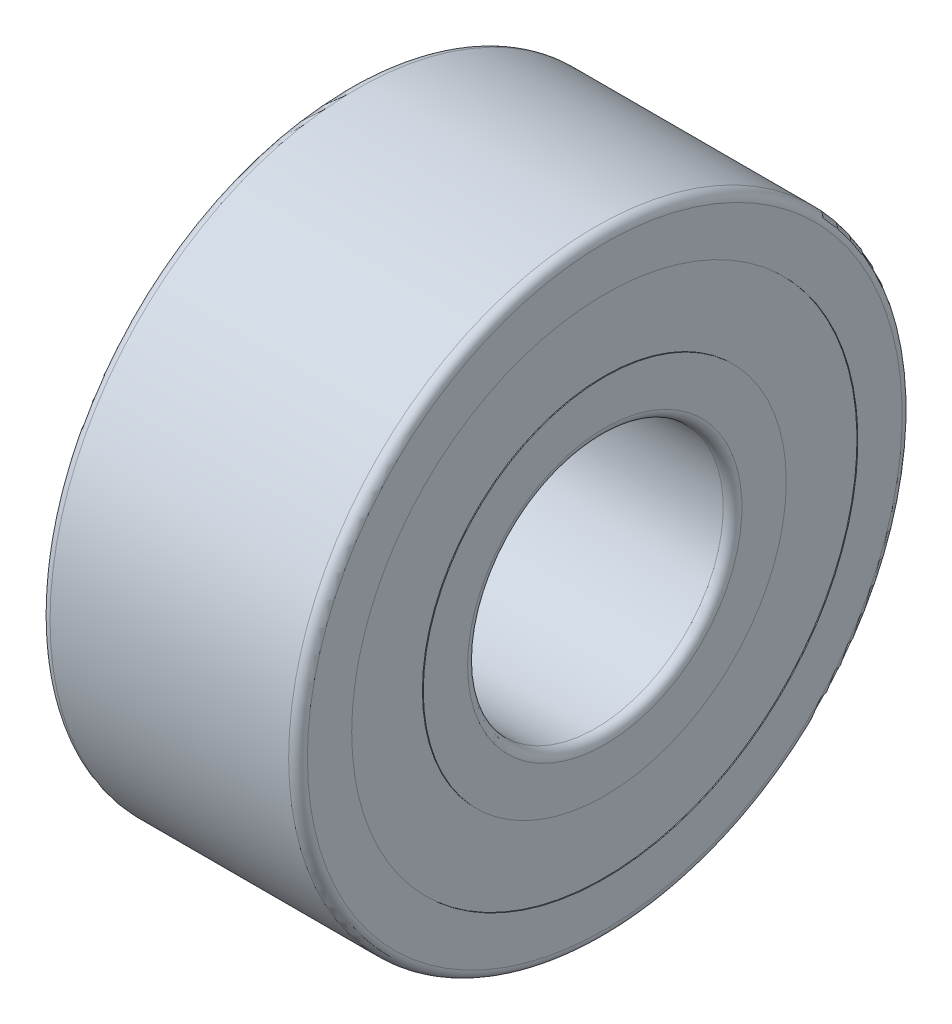
SolidWorks part; units mm, degrees
note: '?' marks a value the reader was unsure of.
ref_plane "基准面1" through (0, 0, 0) normal (0, 0, 1) x (1, 0, 0)
ref_plane "基准面2" through (0, 0, 0) normal (0, 1, 0) x (1, 0, 0)
ref_plane "基准面3" through (0, 0, 0) normal (1, 0, 0) x (0, 0, -1)
sketch "尺寸草图" plane through (0, 0, 0) normal (0, 0, 1) x (1, 0, 0)
  line L0 (0, 0) -> (72, 0) construction
  point P3 (1.1, 0)
  point P4 (30.2, 0)
  point P5 (30, 0)
  dimension "DD" = 72
  dimension "r" = 1.1
  dimension "B" = 30.2
  dimension "d" = 30
sketch "草图1" plane through (0, 0, 0) normal (0, 0, 1) x (1, 0, 0)
  line L0 (0, 0) -> (30.2, 0) construction
  line L1 (0, 0) -> (0, 36) construction
  line L2 (0, 25.5) -> (30.2, 25.5) construction
  line L3 (0, 15) -> (30.2, 15)
  line L4 (0, 36) -> (30.2, 36)
  line L5 (0, 36) -> (0, 15)
  line L6 (30.2, 36) -> (30.2, 15)
  line L7 (7.55, 36) -> (7.55, 15) construction
  line L8 (29.45, 29.7) -> (29.45, 21.3)
  line L9 (15.1, 36) -> (15.1, 15) construction
  line L10 (7.55, 21.3) -> (30.2, 21.3)
  line L11 (7.55, 29.7) -> (30.2, 29.7)
  circle A1 centre (7.55, 25.5) radius 6.3
  circle A3 centre (22.65, 25.5) radius 6.3
  dimension "D4" = 30
  dimension "D2" = 12.6
  dimension "D3" = 30.2
  dimension "D1" = 72
  dimension "D7" = 7.55
  dimension "D9" = 0.75
  dimension "D5" = 4.2
  dimension "D6" = 4.2
sketch "草图2" plane through (0, 0, 0) normal (0, 0, 1) x (1, 0, 0)
  line L2 (0, 36) -> (30.2, 36) construction
  line L3 (7.55, 29.7) -> (30.2, 29.7) construction
  line L4 (30.2, 36) -> (30.2, 15) construction
  line L6 (0, 36) -> (30.2, 36)
  line L7 (0, 29.7) -> (30.2, 29.7)
  line L8 (30.2, 36) -> (30.2, 29.7)
  line L9 (0, 36) -> (0, 29.7)
  line L10 (0, 0) -> (72, 0) construction
  line L11 (0, 0) -> (72, 0) construction
revolve "基体-旋转" add sketch "草图2" angle 360 about L11
sketch "草图4" plane through (0, 0, 0) normal (0, 0, 1) x (1, 0, 0)
  line L0 (0, 36) -> (0, -36) construction
  line L1 (30.2, 36) -> (30.2, 15) construction
  line L2 (7.55, 21.3) -> (30.2, 21.3) construction
  line L3 (0, 0) -> (30.2, 0) construction
  line L4 (12.2457, 21.3) -> (17.9543, 21.3)
  line L5 (0, 15) -> (30.2, 15) construction
  line L6 (30.2, 21.3) -> (30.2, 15)
  line L7 (0, 21.3) -> (2.8543, 21.3)
  line L8 (0, 21.3) -> (0, 15)
  line L9 (0, 15) -> (30.2, 15)
  line L10 (0, 0) -> (30.2, 0) construction
  line L11 (27.3457, 21.3) -> (30.2, 21.3)
  circle A1 centre (22.65, 25.5) radius 6.3 construction
  circle A3 centre (7.55, 25.5) radius 6.3 construction
  arc A4 (17.9543, 21.3) -> (27.3457, 21.3) centre (22.65, 25.5) ccw
  arc A6 (2.8543, 21.3) -> (12.2457, 21.3) centre (7.55, 25.5) ccw
sketch "草图7" plane through (0, 0, 0) normal (0, 0, 1) x (1, 0, 0)
  line L0 (0, 0) -> (72, 0) construction
  line L1 (7.55, 29.7) -> (30.2, 29.7) construction
  line L3 (7.55, 21.3) -> (30.2, 21.3) construction
  line L4 (0, 0) -> (72, 0) construction
  line L5 (12.2457, 29.7) -> (17.9543, 29.7)
  line L11 (12.2457, 21.3) -> (17.9543, 21.3)
  circle A0 centre (22.65, 25.5) radius 6.3 construction
  circle A1 centre (7.55, 25.5) radius 6.3 construction
  arc A2 (17.9543, 21.3) -> (17.9543, 29.7) centre (22.65, 25.5) ccw
  arc A3 (12.2457, 29.7) -> (12.2457, 21.3) centre (7.55, 25.5) ccw
revolve "切除-旋转1" cut sketch "草图7" angle 360 about L4
sketch "草图8" plane through (0, 0, 0) normal (0, 0, 1) x (1, 0, 0)
  line L0 (0, 25.5) -> (30.2, 25.5) construction
  line L1 (0, 25.5) -> (30.2, 25.5) construction
  line L2 (1.2, 25.5) -> (13.9, 25.5)
  circle A1 centre (7.55, 25.5) radius 6.3 construction
  arc A2 (13.85, 25.5) -> (1.25, 25.5) centre (7.55, 25.5) ccw construction
  arc A3 (13.9, 25.5) -> (1.2, 25.5) centre (7.55, 25.5) ccw
  dimension "D1" = 0.05
revolve "凸台-旋转3" add sketch "草图8" angle 360 about L1
revolve "凸台-旋转5" add sketch "草图4" angle 360 about L10
ref_axis "基准轴1" through (80.9, 0, 0) along (-1, 0, 0)?
pattern_circular "阵列(圆周)2" count 10 over 360 about axis through (0, 0, 0) along (1, 0, 0) of "凸台-旋转3"
ref_plane "基准面4" through (15.1, 0, 0) normal (-1, 0, 0) x (0, 0, 1)
mirror "镜向1" about plane through (15.1, 0, 0) normal (-1, 0, 0) of "凸台-旋转3", "阵列(圆周)2"
fillet "圆角2" radius 1.1 4 edges at (0, 0, 15) (30.2, 0, 15) (0, 0, 36) (30.2, 0, 36)
sketch "草图9" plane through (0, 0, 0) normal (0, 0, 1) x (1, 0, 0)
  line L0 (29.45, 29.7) -> (29.45, 21.3) construction
  line L1 (29.45, 29.7) -> (29.45, 21.3)
  line L2 (29.45, 29.7) -> (30.1, 29.7)
  line L3 (7.55, 29.7) -> (30.2, 29.7) construction
  line L4 (30.1, 29.7) -> (30.1, 21.3)
  line L5 (7.55, 21.3) -> (30.2, 21.3) construction
  line L6 (30.1, 21.3) -> (29.45, 21.3)
  line L7 (30.2, 36) -> (30.2, 15) construction
  line L8 (15.1, 0) -> (15.1, 121.4018) construction
  line L9 (0, 0) -> (30.2, 0) construction
  line L10 (15.1, 0) -> (-32.6908, 0) construction
  line L11 (0.1, 21.3) -> (0.75, 21.3)
  line L12 (0.1, 29.7) -> (0.1, 21.3)
  line L13 (0.75, 29.7) -> (0.1, 29.7)
  line L14 (0.75, 29.7) -> (0.75, 21.3)
  dimension "D1" = 0.1
revolve "旋转1" add sketch "草图9" angle 360 about L10
